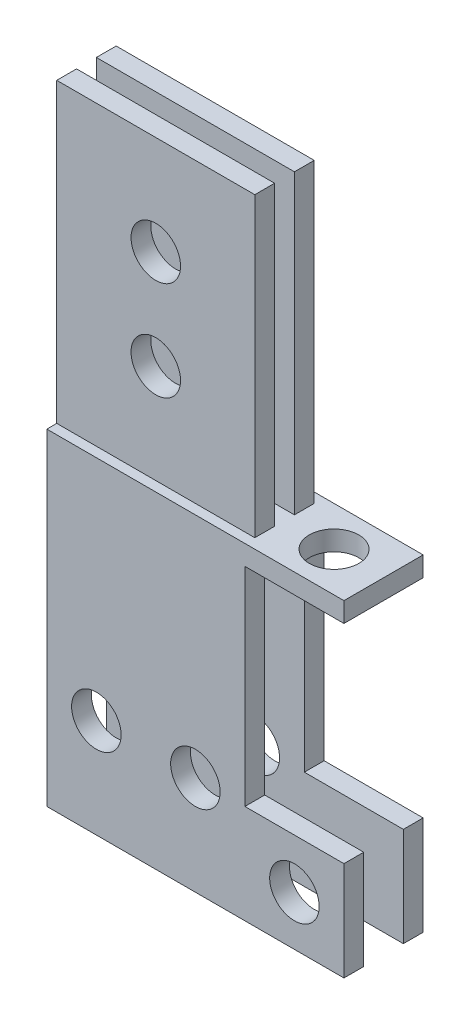
SolidWorks part; units mm, degrees
ref_plane "Front Plane" through (0, 0, 0) normal (0, 0, 1) x (1, 0, 0)
ref_plane "Top Plane" through (0, 0, 0) normal (0, 1, 0) x (1, 0, 0)
ref_plane "Right Plane" through (0, 0, 0) normal (1, 0, 0) x (0, 0, -1)
sketch "Sketch1" plane through (0, 0, 0) normal (0, 0, 1) x (1, 0, 0)
  line L0 (-24.8418, 34.8145) -> (-24.8418, 6.3014) construction
  line L1 (-34.8418, 37.8145) -> (-14.8418, 37.8145)
  line L2 (-34.8418, 37.8145) -> (-34.8418, 34.8145)
  line L3 (-34.8418, 34.8145) -> (-14.8418, 34.8145)
  line L4 (-14.8418, 37.8145) -> (-14.8418, 34.8145)
  line L5 (-34.8418, 37.8145) -> (-14.8418, 37.8145)
  line L6 (-34.8418, 37.8145) -> (-34.8418, 67.8145)
  line L7 (-34.8418, 67.8145) -> (-14.8418, 67.8145)
  line L8 (-14.8418, 37.8145) -> (-14.8418, 67.8145)
  line L9 (-34.8418, 34.8145) -> (-14.8418, 34.8145)
  line L10 (-34.8418, 34.8145) -> (-34.8418, 4.8145)
  line L11 (-34.8418, 4.8145) -> (-14.8418, 4.8145)
  line L12 (-14.8418, 34.8145) -> (-14.8418, 4.8145)
  line L13 (-14.8418, 9.8145) -> (-4.8418, 9.8145) construction
  line L14 (-14.8418, 4.8145) -> (-4.8418, 4.8145)
  line L15 (-14.8418, 4.8145) -> (-14.8418, 14.8145)
  line L16 (-14.8418, 14.8145) -> (-4.8418, 14.8145)
  line L17 (-4.8418, 4.8145) -> (-4.8418, 14.8145)
  line L18 (-9.8418, 14.8145) -> (-9.8418, 4.8145) construction
  line L19 (-34.8418, 14.8145) -> (-14.8418, 14.8145) construction
  line L20 (-34.8418, 19.8145) -> (-14.8418, 19.8145) construction
  line L21 (-24.8418, 67.8145) -> (-24.8418, 37.8145) construction
  line L22 (-34.8418, 52.8145) -> (-14.8418, 52.8145) construction
  circle A0 centre (-9.8418, 9.8145) radius 2.5
  circle A1 centre (-29.8418, 14.8145) radius 2.5
  circle A2 centre (-19.8418, 14.8145) radius 2.5
  circle A3 centre (-24.8418, 57.8145) radius 2.5
  circle A4 centre (-24.8418, 47.8145) radius 2.5
  dimension "D8" = 5
  dimension "D10" = 5
  dimension "D12" = 5
  dimension "D1" = 3
  dimension "D2" = 20
  dimension "D3" = 30
  dimension "D4" = 20
  dimension "D5" = 30
  dimension "D6" = 20
  dimension "D7" = 10
  dimension "D9" = 20
  dimension "D11" = 5
  dimension "D13" = 5
extrude "Lip" add sketch "Sketch1" along normal blind 4 and the other way blind 4 contours L4 L1 L2 L3 region at (-24.8418, 36.3145, 0)
extrude "Side1" add sketch "Sketch1<3>" along normal blind 2 from offset 2 contours L12 L3 L10 L11 A1 A2 | L14 L17 L16 L12 A0 region at (-24.8418, 20.1646, 0) region at (-9.8418, 14.6731, 0)
sketch "Sketch1<3>" plane through (0, 0, 0) normal (0, 0, 1) x (1, 0, 0) same geometry as "Sketch1"
sketch "Sketch2" plane through (0, 37.8145, 0) normal (0, 1, 0) x (1, 0, 0)
  line L0 (-14.8418, 0) -> (-4.8418, 0) construction
  line L1 (-14.8418, -4) -> (-4.8418, -4)
  line L2 (-14.8418, -4) -> (-14.8418, 4)
  line L3 (-14.8418, 4) -> (-4.8418, 4)
  line L4 (-4.8418, -4) -> (-4.8418, 4)
  line L5 (-9.8418, 4) -> (-9.8418, -4) construction
  circle A0 centre (-9.8418, 0) radius 2.5
  dimension "D3" = 5
  dimension "D1" = 8
  dimension "D2" = 10
extrude "Zip2 Hole" add sketch "Sketch2" against normal blind 2
extrude "Side2" add sketch "Sketch1<4>" against normal blind 2 from offset 2 contours L12 L3 L10 L11 A1 A2 | L15 L16 L17 L14 region at (-24.8418, 20.1646, 0) offset against normal yes
sketch "Sketch1<4>" plane through (0, 0, 0) normal (0, 0, 1) x (1, 0, 0) same geometry as "Sketch1"
extrude "Grabber" add sketch "Sketch1<5>" along normal blind 2 from offset 1 contours L1 L8 L7 L6 region at (-24.8418, 52.8145, 0)
sketch "Sketch1<5>" plane through (0, 0, 0) normal (0, 0, 1) x (1, 0, 0) same geometry as "Sketch1"
extrude "Grabber 2" add sketch "Sketch1<6>" against normal blind 2 from offset 1 contours L1 L8 L7 L6 region at (-24.8418, 52.8145, 0) offset against normal yes
sketch "Sketch1<6>" plane through (0, 0, 0) normal (0, 0, 1) x (1, 0, 0) same geometry as "Sketch1"
